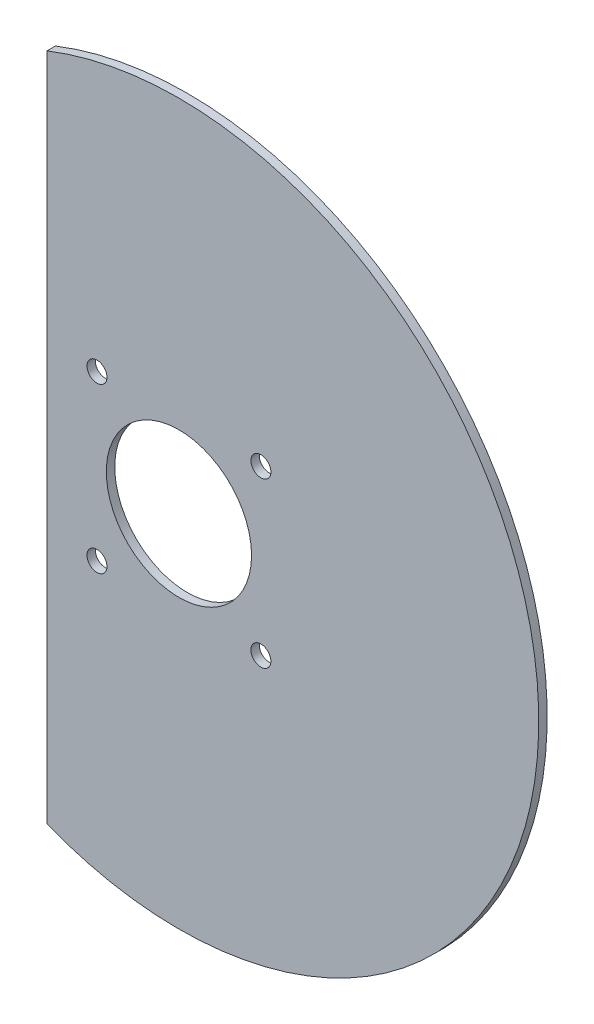
SolidWorks part; units mm, degrees
ref_plane "Front" through (0, 0, 0) normal (0, 0, 1) x (1, 0, 0)
ref_plane "Top" through (0, 0, 0) normal (0, 1, 0) x (1, 0, 0)
ref_plane "Right" through (0, 0, 0) normal (1, 0, 0) x (0, 0, -1)
sketch "Sketch1" plane through (0, 0, 0) normal (0, 0, 1) x (1, 0, 0)
  circle A0 centre (0, 0) radius 55.75
  circle A1 centre (0, 0) radius 11.25
extrude "Extrude1" add sketch "Sketch1" along normal blind 1.3
sketch "Sketch2" plane through (0, 0, 1.3) normal (0, 0, 1) x (1, 0, 0)
  circle A0 centre (12.7, -12.7) radius 1.55
  circle A1 centre (12.7, 12.7) radius 1.55
  circle A2 centre (-12.7, 12.7) radius 1.55
  circle A3 centre (-12.7, -12.7) radius 1.55
extrude "Cut-Extrude1" cut sketch "Sketch2" against normal through all
sketch "Sketch3" plane through (0, 0, 1.3) normal (0, 0, 1) x (1, 0, 0)
  line L0 (-20.4416, 51.8672) -> (-20.4416, -51.8672)
  circle A0 centre (0, 0) radius 55.75 construction
  arc A1 (-20.4416, 51.8672) -> (-20.4416, -51.8672) centre (0, 0) ccw
extrude "Cut-Extrude2" cut sketch "Sketch3" against normal through all
